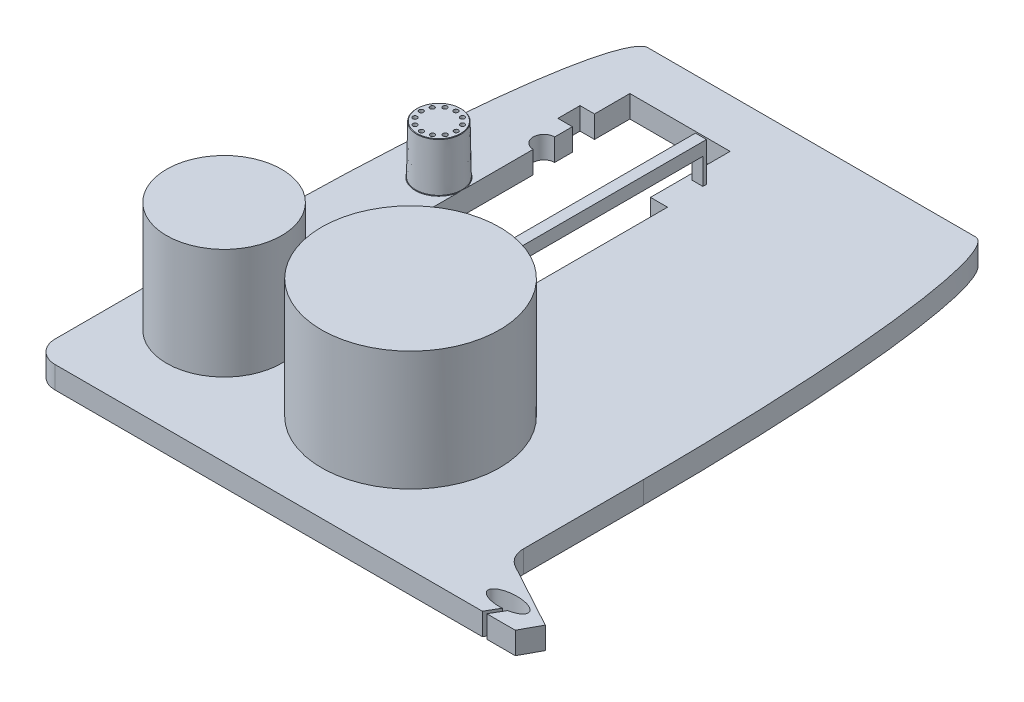
SolidWorks part; units mm, degrees
ref_plane "Front Plane" through (0, 0, 0) normal (0, 0, 1) x (1, 0, 0)
ref_plane "Top Plane" through (0, 0, 0) normal (0, 1, 0) x (1, 0, 0)
ref_plane "Right Plane" through (0, 0, 0) normal (1, 0, 0) x (0, 0, -1)
sketch "Sketch1" plane through (0, 0, 0) normal (0, 1, 0) x (1, 0, 0)
  line L0 (-9.3344, 6.3585) -> (0.0656, 6.3585)
  line L5 (0.0656, 6.3585) -> (0.0656, 19.2585)
  line L6 (0.0656, 19.2585) -> (-9.3344, 19.2585)
  line L7 (-9.3344, 19.2585) -> (-9.3344, 6.3585)
  line L8 (0.0656, 6.3585) -> (1.5656, 6.3585)
  line L9 (1.5656, 6.3585) -> (1.8047, 6.7977)
  line L10 (1.8047, 6.7977) -> (0.0656, 7.7443)
  line L11 (0.0656, 7.7443) -> (0.0656, 6.3585)
  dimension "D1" = 9.4
  dimension "D2" = 12.9
  dimension "D3" = 1.98
  dimension "D4" = 0.5
  dimension "D5" = 1.5
extrude "Boss-Extrude1" add sketch "Sketch1" along normal blind 0.5 contours L9 L10 L5 L8 | L6 L7 L0 L5
fillet "Fillet4" radius 0.5 1 edges at (0.0656, 0.25, -7.7443)
fillet "Fillet7" radius 0.5 1 edges at (-9.3344, 0.25, -6.3585)
sketch "Sketch2" plane through (0, 0.5, 0) normal (0, 1, 0) x (1, 0, 0)
  line L0 (1.8047, 6.7977) -> (0.3266, 7.6023) construction
  ellipse E0 centre (0.9223, 6.8413) end of major axis (0.4696, 6.8413) minor radius 0.2
  dimension "D1" = 0.2
  dimension "D2" = 0.9055
  dimension "D3" = 0.6
fillet "Fillet8" radius 8.5 1 edges at (0.0656, 0.25, -19.2585)
fillet "Fillet9" radius 1 1 edges at (-9.3344, 0.25, -19.2585)
extrude "Cut-Extrude1" cut sketch "Sketch2" against normal blind 0.5
sketch "Sketch3" plane through (0, 0, 0) normal (0, 1, 0) x (1, 0, 0)
  line L0 (1.0963, 6.6566) -> (0.9223, 6.3585)
  line L1 (-8.8344, 6.3585) -> (1.5656, 6.3585) construction
  line L2 (0.9223, 6.3585) -> (0.8223, 6.3585)
  line L3 (0.8223, 6.3585) -> (0.9886, 6.6434)
  line L4 (0.9886, 6.6434) -> (1.0963, 6.6566)
  ellipse E0 centre (0.9223, 6.8413) end of major axis (1.3751, 6.8413) minor radius 0.2 construction
  dimension "D1" = 0.1
extrude "Cut-Extrude2" cut sketch "Sketch3" along normal blind 0.5
sketch "Sketch4" plane through (0, 0.5, 0) normal (0, 1, 0) x (1, 0, 0)
  line L0 (-7.6436, 18.1585) -> (-7.6436, 17.3585)
  line L1 (-7.6436, 17.3585) -> (-7.9707, 17.3585)
  line L2 (-7.9707, 17.3585) -> (-7.9707, 16.8585)
  line L3 (-7.9707, 16.8585) -> (-7.6436, 16.8585)
  line L4 (-7.6436, 16.8585) -> (-7.6436, 16.4585)
  line L5 (-7.6436, 15.974) -> (-7.6436, 11.874)
  line L6 (-7.6436, 11.874) -> (-6.1936, 11.4684)
  line L7 (-6.1936, 11.4684) -> (-4.9936, 11.4684)
  line L8 (-4.9936, 11.9045) -> (-4.9936, 12.5707)
  line L9 (-4.9936, 12.5707) -> (-4.9936, 16.3585)
  line L10 (-4.9936, 16.3585) -> (-5.3784, 16.3585)
  line L11 (-5.3784, 16.3585) -> (-5.3784, 18.1585)
  line L12 (-5.3784, 18.1585) -> (-7.6436, 18.1585)
  line L13 (-0.9344, 19.2585) -> (-8.3344, 19.2585) construction
  arc A0 (-7.6436, 16.4585) -> (-7.6436, 15.974) centre (-7.6436, 16.2162) ccw
  arc A1 (-4.9936, 11.4684) -> (-4.9936, 11.9045) centre (-4.9936, 11.6865) ccw
  dimension "D1" = 1.1
  dimension "D2" = 0.8
  dimension "D3" = 0.5
  dimension "D4" = 0.4
  dimension "D5" = 4.1
  dimension "D6" = 1.45
  dimension "D7" = 1.2
  dimension "D8" = 1.8
extrude "Cut-Extrude3" cut sketch "Sketch4" against normal blind 0.5
ref_plane "Lever" through (-5, 0, 0) normal (-1, 0, 0) x (0, 0, 1)
sketch "Sketch5" plane through (-5, 0, 0) normal (-1, 0, 0) x (0, 0, 1)
  line L0 (-17.2468, 0.5) -> (-17.2468, 1.3774)
  line L1 (-10.7585, 0.5) -> (-19.2585, 0.5) construction
  line L2 (-17.2468, 1.3774) -> (-8.8863, 1.3774)
  line L3 (-8.8863, 1.0891) -> (-17.1645, 1.0891)
  line L4 (-17.1645, 1.0891) -> (-17.1645, 0.5)
  line L5 (-17.1645, 0.5) -> (-17.2468, 0.5)
  arc A0 (-8.8863, 1.0891) -> (-8.8863, 1.3774) centre (-8.8863, 1.2333) ccw
extrude "Boss-Extrude2" add sketch "Sketch5" along normal blind 0.25
ref_plane "Plane2" through (0, 0.5, 0) normal (0, 1, 0) x (1, 0, 0)
sketch "Sketch6" plane through (0, 0.5, 0) normal (0, 1, 0) x (1, 0, 0)
  circle A0 centre (-8.1645, 14.3621) radius 0.5
  point P2 (-8.1645, 14.3621)
  dimension "D1" = 1
extrude "Boss-Extrude3" add sketch "Sketch6" along normal blind 0.7
ref_plane "Plane3" through (0, 1.2, 0) normal (0, 1, 0) x (1, 0, 0)
sketch "Sketch7" plane through (0, 1.2, 0) normal (0, 1, 0) x (1, 0, 0)
  circle A0 centre (-8.1645, 14.3621) radius 0.5
extrude "Boss-Extrude4" add sketch "Sketch7" along normal blind 0.4
draft "Draft1" type of draft neutral plane draft angle 1 faces to draft 1 face at (-8.1645, 0.5, -13.8621) neutral plane through (-8.1645, 1.6, -14.3621) neutral plane normal (0, 1, 0) parameters "D1"=1
sketch "Sketch17" plane through (0, 1.6, 0) normal (0, 1, 0) x (1, 0, 0)
  circle A0 centre (-8.1665, 14.7505) radius 0.05
  dimension "D1" = 0.1
extrude "Cut-Extrude6" cut sketch "Sketch17" against normal blind 0.2
pattern_circular "CirPattern1" count 12 over 360 about axis through (-8.1644, 0, -14.3582) along (0, 1, 0) of "Cut-Extrude6"
chamfer "Chamfer3" distance 0.01 angle 45 2 edges at (-8.1645, 1.6, -13.8621) (-8.1645, 0.5, -13.8429)
sketch "Sketch22" plane through (0, 0.5, 0) normal (0, 1, 0) x (1, 0, 0)
  circle A0 centre (-7.5974, 8.9409) radius 1.3
  circle A1 centre (-3.0106, 8.9409) radius 1.5
  dimension "D1" = 3
  dimension "D2" = 2.6
extrude "Boss-Extrude6" add sketch "Sketch22" along normal blind 2.5 contours A0
sketch "Sketch23" plane through (0, 0.5, 0) normal (0, 1, 0) x (1, 0, 0)
  circle A0 centre (-3.1011, 8.6592) radius 0.9
  dimension "D1" = 1.8
extrude "Boss-Extrude8" add sketch "Sketch23" along normal blind 0.7
sketch "Sketch24" plane through (0, 1.2, 0) normal (0, 1, 0) x (1, 0, 0)
  circle A0 centre (-3.1011, 8.6592) radius 2.012
extrude "Boss-Extrude9" add sketch "Sketch24" along normal blind 2.7
fillet "Fillet12" radius 0.1 1 edges at (-7.6436, 0.25, -11.874)
sketch "Sketch26" plane through (0, 0.5, 0) normal (0, 1, 0) x (1, 0, 0)
  arc A0 (-3.1159, 10.6711) -> (-3.0736, 10.671) centre (-3.0947, 10.671) ccw
  circle A1 centre (-3.1011, 8.6592) radius 2.012 construction
ref_plane "Plane6" through (0, 3.9, 0) normal (0, 1, 0) x (1, 0, 0)
equation "\"3..50mm\"=0.5"
